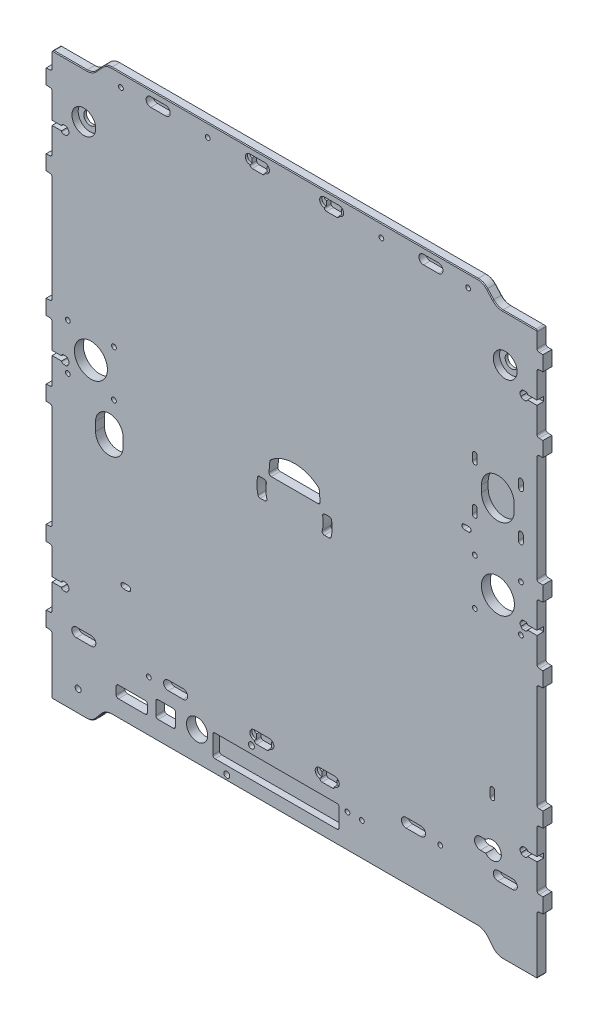
SolidWorks part; units mm, degrees
ref_plane "Alzado" through (0, 0, 0) normal (0, 0, 1) x (1, 0, 0)
ref_plane "Planta" through (0, 0, 0) normal (0, 1, 0) x (1, 0, 0)
ref_plane "Vista lateral" through (0, 0, 0) normal (1, 0, 0) x (0, 0, -1)
ref_plane "Plano1" through (0, 0, 3) normal (0, 0, 1) x (1, 0, 0)
sketch "Croquis1" plane through (0, 0, 3) normal (0, 0, 1) x (1, 0, 0)
  line L0 (-167.1, 194) -> (-167.1, -194)
  line L1 (-167.1, -194) -> (167.1, -194)
  line L2 (167.1, -194) -> (167.1, 194)
  line L3 (167.1, 194) -> (-167.1, 194)
  dimension "D1" = 334.2
  dimension "D2" = 388
extrude "Saliente-Extruir1" add sketch "Croquis1" against normal blind 6
sketch "Croquis2" plane through (0, 0, 3) normal (0, 0, 1) x (1, 0, 0)
  line L0 (-17, -151.6) -> (-17, -150.1)
  line L1 (-17, -143.9) -> (-27, -143.9)
  line L2 (-27, -150.1) -> (-27, -151.6)
  line L3 (-27, -151.6) -> (-17, -151.6)
  line L5 (167.1, 194) -> (-167.1, 194) construction
  arc A0 (-17, -150.1) -> (-17, -143.9) centre (-17, -147) ccw
  arc A1 (-27, -143.9) -> (-27, -150.1) centre (-27, -147) ccw
  dimension "D1" = 3.1
  dimension "D3" = 345.6
extrude "Cortar-Extruir1" cut sketch "Croquis2" against normal blind 1.5
sketch "Croquis3" plane through (0, 0, 1.5) normal (0, 0, 1) x (1, 0, 0)
  line L0 (-17, -143.9) -> (-27, -143.9)
  line L1 (-27, -146.9) -> (-27, -151.6)
  line L2 (-27, -151.6) -> (-17, -151.6)
  line L3 (-17, -151.6) -> (-17, -146.9)
  arc A0 (-17, -146.9) -> (-17, -143.9) centre (-17, -145.4) ccw
  arc A1 (-27, -143.9) -> (-27, -146.9) centre (-27, -145.4) ccw
  dimension "D1" = 1.5
  dimension "D2" = 1.5
extrude "Cortar-Extruir2" cut sketch "Croquis3" against normal blind 3
sketch "Croquis4" plane through (0, 0, 3) normal (0, 0, 1) x (1, 0, 0)
  line L0 (-20, 182.4) -> (-20, 183.9)
  line L1 (-20, 190.1) -> (-30, 190.1)
  line L2 (-30, 183.9) -> (-30, 182.4)
  line L3 (-30, 182.4) -> (-20, 182.4)
  line L4 (-27, -150.1) -> (-27, -151.6) construction
  line L5 (-27, -151.6) -> (-17, -151.6) construction
  arc A0 (-20, 183.9) -> (-20, 190.1) centre (-20, 187) ccw
  arc A1 (-30, 190.1) -> (-30, 183.9) centre (-30, 187) ccw
  dimension "D1" = 3.1
  dimension "D2" = 7
  dimension "D3" = 3
  dimension "D4" = 334
  dimension "D5" = 338.6
extrude "Cortar-Extruir3" cut sketch "Croquis4" against normal blind 1.5
sketch "Croquis5" plane through (0, 0, 1.5) normal (0, 0, 1) x (1, 0, 0)
  line L0 (-30, 187.1) -> (-30, 182.4)
  line L1 (-30, 182.4) -> (-20, 182.4)
  line L2 (-20, 182.4) -> (-20, 187.1)
  line L3 (-20, 190.1) -> (-30, 190.1)
  line L4 (-20, 182.4) -> (-20, 183.9) construction
  arc A0 (-30, 190.1) -> (-30, 187.1) centre (-30, 188.6) ccw
  arc A1 (-20, 187.1) -> (-20, 190.1) centre (-20, 188.6) ccw
  dimension "D1" = 1.5
  dimension "D2" = 10
extrude "Cortar-Extruir4" cut sketch "Croquis5" against normal blind 3
sketch "Croquis6" plane through (0, 0, -3) normal (0, 0, -1) x (-1, 0, 0)
  line L0 (167.1, 121.8397) -> (167.1, 161.5603)
  line L1 (167.1, 161.5603) -> (163.1, 161.5603)
  line L2 (163.1, 161.5603) -> (163.1, 121.8397)
  line L3 (163.1, 121.8397) -> (167.1, 121.8397)
  line L4 (-167.1, -194) -> (-167.1, 194) construction
  line L5 (-167.1, 194) -> (167.1, 194) construction
  dimension "D1" = 330.2
  dimension "D2" = 334.2
  dimension "D3" = 32.4397
  dimension "D4" = 72.1603
extrude "Cortar-Extruir5" cut sketch "Croquis6" against normal through all
sketch "Croquis7" plane through (0, 0, -3) normal (0, 0, -1) x (-1, 0, 0)
  line L0 (167.1, -12.3603) -> (167.1, 27.3603)
  line L1 (167.1, 27.3603) -> (163.1, 27.3603)
  line L2 (163.1, 27.3603) -> (163.1, -12.3603)
  line L3 (163.1, -12.3603) -> (167.1, -12.3603)
  line L4 (163.1, 161.5603) -> (163.1, 121.8397) construction
  line L5 (167.1, 161.5603) -> (163.1, 161.5603) construction
  dimension "D1" = 4
  dimension "D2" = 134.2
  dimension "D3" = 173.9206
extrude "Cortar-Extruir6" cut sketch "Croquis7" against normal through all
sketch "Croquis8" plane through (0, 0, -3) normal (0, 0, -1) x (-1, 0, 0)
  line L0 (167.1, -144.0603) -> (167.1, -104.3397)
  line L1 (167.1, -104.3397) -> (163.1, -104.3397)
  line L2 (163.1, -104.3397) -> (163.1, -144.0603)
  line L3 (163.1, -144.0603) -> (167.1, -144.0603)
  line L4 (167.1, 121.8397) -> (167.1, 27.3603) construction
  line L5 (163.1, 121.8397) -> (167.1, 121.8397) construction
  dimension "D1" = 4
  dimension "D2" = 226.1794
  dimension "D3" = 265.9
extrude "Cortar-Extruir7" cut sketch "Croquis8" against normal through all
sketch "Croquis9" plane through (0, 0, 3) normal (0, 0, 1) x (1, 0, 0)
  line L0 (-163.1, -125.8) -> (-156.779, -125.8)
  line L1 (-155.3, -127.05) -> (-153.9, -127.05)
  line L2 (-152.421, -125.8) -> (-152.421, -125.6375)
  line L3 (-152.421, -122.9625) -> (-152.421, -122.8)
  line L4 (-153.9, -121.55) -> (-155.3, -121.55)
  line L5 (-156.779, -122.8) -> (-163.1, -122.8)
  line L6 (-163.1, -122.8) -> (-163.1, -125.8)
  line L7 (-167.1, -144.0603) -> (-167.1, -194) construction
  line L8 (-167.1, -194) -> (167.1, -194) construction
  arc A0 (-156.779, -125.8) -> (-155.3, -127.05) centre (-155.3, -125.55) ccw
  arc A1 (-153.9, -127.05) -> (-152.421, -125.8) centre (-153.9, -125.55) ccw
  arc A2 (-152.421, -125.6375) -> (-152.421, -122.9625) centre (-153.1, -124.3) ccw
  arc A3 (-152.421, -122.8) -> (-153.9, -121.55) centre (-153.9, -123.05) ccw
  arc A4 (-155.3, -121.55) -> (-156.779, -122.8) centre (-155.3, -123.05) ccw
  dimension "D1" = 1.5
  dimension "D2" = 1.5
  dimension "D3" = 1.5
  dimension "D4" = 4
  dimension "D5" = 10.321
  dimension "D6" = 11.8
  dimension "D7" = 13.2
  dimension "D8" = 14
  dimension "D9" = 68.3625
extrude "Cortar-Extruir8" cut sketch "Croquis9" against normal blind 4.5
sketch "Croquis10" plane through (0, 0, 3) normal (0, 0, 1) x (1, 0, 0)
  line L0 (-163.1, 6.1) -> (-156.7795, 6.1)
  line L1 (-155.3004, 4.85) -> (-153.9004, 4.85)
  line L2 (-152.4214, 6.1) -> (-152.4214, 6.2625)
  line L3 (-152.4214, 8.9375) -> (-152.4214, 9.1)
  line L4 (-153.9004, 10.35) -> (-155.3004, 10.35)
  line L5 (-156.7795, 9.1) -> (-163.1, 9.1)
  line L6 (-163.1, 9.1) -> (-163.1, 6.1)
  line L7 (-167.1, -144.0603) -> (-167.1, -194) construction
  line L8 (-167.1, -194) -> (167.1, -194) construction
  arc A0 (-156.7795, 6.1) -> (-155.3004, 4.85) centre (-155.3004, 6.35) ccw
  arc A1 (-153.9004, 4.85) -> (-152.4214, 6.1) centre (-153.9004, 6.35) ccw
  arc A2 (-152.4214, 6.2625) -> (-152.4214, 8.9375) centre (-153.1004, 7.6) ccw
  arc A3 (-152.4214, 9.1) -> (-153.9004, 10.35) centre (-153.9004, 8.85) ccw
  arc A4 (-155.3004, 10.35) -> (-156.7795, 9.1) centre (-155.3004, 8.85) ccw
  dimension "D1" = 1.5
  dimension "D2" = 1.5
  dimension "D3" = 1.5
  dimension "D4" = 4
  dimension "D5" = 200.2625
  dimension "D6" = 201.6
  dimension "D8" = 13.9996
extrude "Cortar-Extruir9" cut sketch "Croquis10" against normal blind 4.5
sketch "Croquis11" plane through (0, 0, 3) normal (0, 0, 1) x (1, 0, 0)
  line L0 (-163.1, 140.2) -> (-156.779, 140.2)
  line L1 (-155.3, 138.95) -> (-153.9, 138.95)
  line L2 (-152.421, 140.2) -> (-152.421, 140.3625)
  line L3 (-152.421, 143.0375) -> (-152.421, 143.2)
  line L4 (-153.9, 144.45) -> (-155.3, 144.45)
  line L5 (-156.779, 143.2) -> (-163.1, 143.2)
  line L6 (-163.1, 143.2) -> (-163.1, 140.2)
  line L7 (-167.1, -12.3603) -> (-167.1, -104.3397) construction
  line L8 (-155.3, -127.05) -> (-153.9, -127.05) construction
  arc A0 (-156.779, 140.2) -> (-155.3, 138.95) centre (-155.3, 140.45) ccw
  arc A1 (-153.9, 138.95) -> (-152.421, 140.2) centre (-153.9, 140.45) ccw
  arc A2 (-152.421, 140.3625) -> (-152.421, 143.0375) centre (-153.1, 141.7) ccw
  arc A3 (-152.421, 143.2) -> (-153.9, 144.45) centre (-153.9, 142.95) ccw
  arc A4 (-155.3, 144.45) -> (-156.779, 143.2) centre (-155.3, 142.95) ccw
  dimension "D1" = 1.5
  dimension "D2" = 1.5
  dimension "D3" = 1.5
  dimension "D4" = 4
  dimension "D5" = 266
  dimension "D6" = 267.25
  dimension "D7" = 267.4125
  dimension "D8" = 14
  dimension "D9" = 268.75
  dimension "D10" = 270
extrude "Cortar-Extruir10" cut sketch "Croquis11" against normal blind 4.5
sketch "Croquis12" plane through (0, 0, -3) normal (0, 0, -1) x (-1, 0, 0)
  line L0 (126.9478, 194) -> (126.9478, 184)
  line L1 (126.9478, 184) -> (167.1, 184)
  line L2 (167.1, 184) -> (167.1, 194)
  line L3 (167.1, 194) -> (126.9478, 194)
  line L4 (163.1, 27.3603) -> (163.1, -12.3603) construction
  line L5 (167.1, 27.3603) -> (163.1, 27.3603) construction
  dimension "D1" = 4
  dimension "D2" = 36.1522
  dimension "D3" = 156.6397
  dimension "D4" = 166.6397
extrude "Cortar-Extruir11" cut sketch "Croquis12" against normal through all
sketch "Croquis13" plane through (0, 0, -3) normal (0, 0, -1) x (-1, 0, 0)
  line L0 (163.1, 171.8397) -> (167.1, 171.8397)
  line L1 (167.1, 171.8397) -> (167.1, 184)
  line L2 (167.1, 184) -> (163.1, 184)
  line L3 (163.1, 184) -> (163.1, 171.8397)
  line L4 (167.1, -144.0603) -> (167.1, -194) construction
  line L5 (167.1, -194) -> (-167.1, -194) construction
  dimension "D1" = 4
  dimension "D2" = 365.8397
  dimension "D3" = 378
extrude "Cortar-Extruir12" cut sketch "Croquis13" against normal through all
sketch "Croquis14" plane through (0, 0, -3) normal (0, 0, -1) x (-1, 0, 0)
  line L0 (167.1, 37.6397) -> (167.1, 111.5603)
  line L1 (167.1, 111.5603) -> (163.1, 111.5603)
  line L2 (163.1, 111.5603) -> (163.1, 37.6397)
  line L3 (163.1, 37.6397) -> (167.1, 37.6397)
  line L4 (167.1, -144.0603) -> (167.1, -194) construction
  line L5 (167.1, -194) -> (-167.1, -194) construction
  dimension "D1" = 4
  dimension "D2" = 231.6397
  dimension "D3" = 305.5603
extrude "Cortar-Extruir13" cut sketch "Croquis14" against normal through all
sketch "Croquis15" plane through (0, 0, -3) normal (0, 0, -1) x (-1, 0, 0)
  line L0 (167.1, -94.0603) -> (167.1, -22.6397)
  line L1 (167.1, -22.6397) -> (163.1, -22.6397)
  line L2 (163.1, -22.6397) -> (163.1, -94.0603)
  line L3 (163.1, -94.0603) -> (167.1, -94.0603)
  line L4 (167.1, 171.8397) -> (167.1, 161.5603) construction
  line L5 (126.9478, 184) -> (163.1, 184) construction
  dimension "D1" = 4
  dimension "D2" = 206.6397
  dimension "D3" = 278.0603
extrude "Cortar-Extruir14" cut sketch "Croquis15" against normal through all
sketch "Croquis16" plane through (0, 0, -3) normal (0, 0, -1) x (-1, 0, 0)
  line L0 (167.1, -154.3397) -> (163.1, -154.3397)
  line L1 (163.1, -154.3397) -> (163.1, -194)
  line L2 (163.1, -194) -> (167.1, -194)
  line L3 (167.1, -194) -> (167.1, -154.3397)
  line L4 (167.1, 121.8397) -> (167.1, 111.5603) construction
  line L5 (163.1, 121.8397) -> (167.1, 121.8397) construction
  dimension "D1" = 4
  dimension "D2" = 276.1794
  dimension "D3" = 315.8397
extrude "Cortar-Extruir15" cut sketch "Croquis16" against normal through all
sketch "Croquis17" plane through (0, 0, -3) normal (0, 0, -1) x (-1, 0, 0)
  line L0 (126.9478, -194) -> (126.9478, -183.0928)
  line L1 (126.9478, -183.0928) -> (-126.9478, -183.0928)
  line L2 (-126.9478, -183.0928) -> (-126.9478, -194)
  line L3 (-126.9478, -194) -> (126.9478, -194)
  line L4 (167.1, -144.0603) -> (167.1, -154.3397) construction
  line L5 (163.1, -194) -> (-167.1, -194) construction
  dimension "D1" = 40.1522
  dimension "D2" = 294.0478
  dimension "D3" = 10.9072
extrude "Cortar-Extruir16" cut sketch "Croquis17" against normal through all
sketch "Croquis18" plane through (0, 0, 3) normal (0, 0, 1) x (1, 0, 0)
  line L0 (-99.03, -171.55) -> (-99.03, -163.55)
  line L1 (-99.03, -163.55) -> (-120.03, -163.55)
  line L2 (-120.03, -163.55) -> (-120.03, -171.55)
  line L3 (-120.03, -171.55) -> (-99.03, -171.55)
  line L4 (167.1, -194) -> (167.1, 194) construction
  line L5 (126.9478, -194) -> (167.1, -194) construction
  dimension "D1" = 266.13
  dimension "D2" = 287.13
  dimension "D3" = 22.45
  dimension "D4" = 30.45
extrude "Cortar-Extruir17" cut sketch "Croquis18" against normal through all
sketch "Croquis19" plane through (0, 0, 3) normal (0, 0, 1) x (1, 0, 0)
  line L0 (-80.15, -170.25) -> (-80.15, -158.75)
  line L1 (-80.15, -158.75) -> (-93.35, -158.75)
  line L2 (-93.35, -158.75) -> (-93.35, -170.25)
  line L3 (-93.35, -170.25) -> (-80.15, -170.25)
  line L4 (167.1, -194) -> (167.1, 194) construction
  line L5 (126.9478, -194) -> (167.1, -194) construction
  dimension "D1" = 247.25
  dimension "D2" = 260.45
  dimension "D3" = 23.75
  dimension "D4" = 35.25
extrude "Cortar-Extruir18" cut sketch "Croquis19" against normal through all
sketch "Croquis20" plane through (0, 0, 3) normal (0, 0, 1) x (1, 0, 0)
  line L0 (153.8846, 55.25) -> (153.8846, 59.75)
  line L1 (150.6846, 59.75) -> (150.6846, 55.25)
  line L2 (167.1, -194) -> (167.1, 194) construction
  line L3 (126.9478, -194) -> (167.1, -194) construction
  arc A0 (153.8846, 59.75) -> (150.6846, 59.75) centre (152.2846, 59.75) ccw
  arc A1 (150.6846, 55.25) -> (153.8846, 55.25) centre (152.2846, 55.25) ccw
  dimension "D1" = 1.6
  dimension "D2" = 14.8154
  dimension "D3" = 249.25
  dimension "D4" = 253.75
extrude "Cortar-Extruir19" cut sketch "Croquis20" against normal through all
sketch "Croquis21" plane through (0, 0, 3) normal (0, 0, 1) x (1, 0, 0)
  line L0 (150.6846, 90.75) -> (150.6846, 86.25)
  line L1 (153.8846, 86.25) -> (153.8846, 90.75)
  line L2 (167.1, -194) -> (167.1, 194) construction
  line L3 (126.9478, -194) -> (167.1, -194) construction
  arc A0 (150.6846, 86.25) -> (153.8846, 86.25) centre (152.2846, 86.25) ccw
  arc A1 (153.8846, 90.75) -> (150.6846, 90.75) centre (152.2846, 90.75) ccw
  dimension "D1" = 1.6
  dimension "D2" = 14.8154
  dimension "D3" = 280.25
  dimension "D4" = 284.75
extrude "Cortar-Extruir20" cut sketch "Croquis21" against normal through all
sketch "Croquis22" plane through (0, 0, 3) normal (0, 0, 1) x (1, 0, 0)
  line L0 (122.8846, 55.25) -> (122.8846, 59.75)
  line L1 (119.6846, 59.75) -> (119.6846, 55.25)
  line L2 (167.1, -194) -> (167.1, 194) construction
  line L3 (126.9478, -194) -> (167.1, -194) construction
  arc A0 (122.8846, 59.75) -> (119.6846, 59.75) centre (121.2846, 59.75) ccw
  arc A1 (119.6846, 55.25) -> (122.8846, 55.25) centre (121.2846, 55.25) ccw
  dimension "D1" = 1.6
  dimension "D2" = 45.8154
  dimension "D3" = 249.25
  dimension "D4" = 253.75
extrude "Cortar-Extruir21" cut sketch "Croquis22" against normal through all
sketch "Croquis23" plane through (0, 0, 3) normal (0, 0, 1) x (1, 0, 0)
  line L0 (119.6846, 90.75) -> (119.6846, 86.25)
  line L1 (122.8846, 86.25) -> (122.8846, 90.75)
  line L2 (167.1, -194) -> (167.1, 194) construction
  line L3 (126.9478, -194) -> (167.1, -194) construction
  arc A0 (119.6846, 86.25) -> (122.8846, 86.25) centre (121.2846, 86.25) ccw
  arc A1 (122.8846, 90.75) -> (119.6846, 90.75) centre (121.2846, 90.75) ccw
  dimension "D1" = 1.6
  dimension "D2" = 45.8154
  dimension "D3" = 280.25
  dimension "D4" = 284.75
extrude "Cortar-Extruir22" cut sketch "Croquis23" against normal through all
sketch "Croquis24" plane through (0, 0, 3) normal (0, 0, 1) x (1, 0, 0)
  line L0 (-133.85, -17.6) -> (-133.85, -23.6)
  line L1 (-115.35, -23.6) -> (-115.35, -17.6)
  line L2 (167.1, -194) -> (167.1, 194) construction
  line L3 (126.9478, -194) -> (167.1, -194) construction
  arc A0 (-133.85, -23.6) -> (-115.35, -23.6) centre (-124.6, -23.6) ccw
  arc A1 (-115.35, -17.6) -> (-133.85, -17.6) centre (-124.6, -17.6) ccw
  dimension "D1" = 9.25
  dimension "D2" = 291.7
  dimension "D3" = 170.4
  dimension "D4" = 176.4
extrude "Cortar-Extruir23" cut sketch "Croquis24" against normal through all
sketch "Croquis25" plane through (0, 0, 3) normal (0, 0, 1) x (1, 0, 0)
  line L0 (-17.3459, 9.2964) -> (17.3459, 9.2964)
  line L1 (17.3459, 9.2964) -> (16.5432, 18.4711)
  line L2 (-16.5432, 18.4711) -> (-17.3459, 9.2964)
  line L3 (167.1, -194) -> (167.1, 194) construction
  line L4 (126.9478, -194) -> (167.1, -194) construction
  arc A0 (16.5432, 18.4711) -> (-16.5432, 18.4711) centre (0, 0) ccw
  dimension "D1" = 24.7964
  dimension "D2" = 149.7541
  dimension "D3" = 150.5568
  dimension "D4" = 167.1
  dimension "D5" = 194
  dimension "D6" = 184.4459
  dimension "D7" = 203.2964
extrude "Cortar-Extruir24" cut sketch "Croquis25" against normal through all
sketch "Croquis26" plane through (0, 0, 3) normal (0, 0, 1) x (1, 0, 0)
  line L0 (-24.3086, -7) -> (-20.0559, -7)
  line L1 (-18.496, 5.5) -> (-24.6913, 5.5)
  line L2 (167.1, -194) -> (167.1, 194) construction
  line L3 (126.9478, -194) -> (167.1, -194) construction
  arc A0 (-24.6913, 5.5) -> (-24.3086, -7) centre (0, 0) ccw
  arc A1 (-20.0559, -7) -> (-18.6094, -5.1033) centre (-20.0559, -5.5) ccw
  arc A2 (-18.6094, -5.1033) -> (-18.496, 5.5) centre (0, 0) cw
  dimension "D1" = 25.2964
  dimension "D2" = 1.5
  dimension "D3" = 19.2964
  dimension "D4" = 167.1
  dimension "D5" = 185.596
  dimension "D6" = 185.7094
  dimension "D7" = 187
extrude "Cortar-Extruir25" cut sketch "Croquis26" against normal through all
sketch "Croquis27" plane through (0, 0, 3) normal (0, 0, 1) x (1, 0, 0)
  line L0 (125.1, -138) -> (128.6279, -138)
  line L1 (128.6279, -130) -> (125.1, -130)
  line L2 (167.1, -194) -> (167.1, 194) construction
  arc A0 (128.6279, -138) -> (128.6279, -130) centre (133.1, -134) cw
  arc A1 (125.1, -130) -> (125.1, -138) centre (125.1, -134) ccw
  dimension "D1" = 6
  dimension "D2" = 4
  dimension "D3" = 34
  dimension "D5" = 42
extrude "Cortar-Extruir26" cut sketch "Croquis27" against normal through all
sketch "Croquis28" plane through (0, 0, 3) normal (0, 0, 1) x (1, 0, 0)
  line L0 (131.6, -98.5) -> (131.6, -103.5)
  line L1 (134.6, -103.5) -> (134.6, -98.5)
  line L2 (167.1, -194) -> (167.1, 194) construction
  line L3 (126.9478, -194) -> (167.1, -194) construction
  arc A0 (131.6, -103.5) -> (134.6, -103.5) centre (133.1, -103.5) ccw
  arc A1 (134.6, -98.5) -> (131.6, -98.5) centre (133.1, -98.5) ccw
  dimension "D1" = 1.5
  dimension "D2" = 34
  dimension "D3" = 90.5
  dimension "D4" = 95.5
extrude "Cortar-Extruir27" cut sketch "Croquis28" against normal through all
sketch "Croquis29" plane through (0, 0, 3) normal (0, 0, 1) x (1, 0, 0)
  line L0 (114.1289, 43.4) -> (117.1289, 43.4)
  line L1 (117.1289, 46.6) -> (114.1289, 46.6)
  line L2 (167.1, -194) -> (167.1, 194) construction
  line L3 (126.9478, -194) -> (167.1, -194) construction
  arc A0 (117.1289, 43.4) -> (117.1289, 46.6) centre (117.1289, 45) ccw
  arc A1 (114.1289, 46.6) -> (114.1289, 43.4) centre (114.1289, 45) ccw
  dimension "D1" = 1.6
  dimension "D2" = 49.9711
  dimension "D3" = 52.9711
  dimension "D4" = 239
extrude "Cortar-Extruir28" cut sketch "Croquis29" against normal through all
sketch "Croquis30" plane through (0, 0, -3) normal (0, 0, -1) x (-1, 0, 0)
  line L0 (115, -102.25) -> (112, -102.25)
  line L1 (112, -105.75) -> (115, -105.75)
  line L2 (133.85, -17.6) -> (133.85, -23.6) construction
  line L3 (-125.1, -138) -> (-128.6279, -138) construction
  arc A0 (112, -102.25) -> (112, -105.75) centre (112, -104) ccw
  arc A1 (115, -105.75) -> (115, -102.25) centre (115, -104) ccw
  dimension "D1" = 1.75
  dimension "D2" = 18.85
  dimension "D3" = 21.85
  dimension "D4" = 34
extrude "Cortar-Extruir29" cut sketch "Croquis30" against normal through all
sketch "Croquis31" plane through (0, 0, 3) normal (0, 0, 1) x (1, 0, 0)
  line L0 (147.7846, 70.75) -> (147.7846, 75.25)
  line L1 (125.7846, 75.25) -> (125.7846, 70.75)
  line L2 (167.1, -194) -> (167.1, 194) construction
  line L3 (126.9478, -194) -> (167.1, -194) construction
  arc A0 (125.7846, 70.75) -> (147.7846, 70.75) centre (136.7846, 70.75) ccw
  arc A1 (147.7846, 75.25) -> (125.7846, 75.25) centre (136.7846, 75.25) ccw
  dimension "D1" = 11
  dimension "D2" = 30.3154
  dimension "D3" = 264.75
  dimension "D4" = 269.25
extrude "Cortar-Extruir30" cut sketch "Croquis31" against normal blind 4.5
sketch "Croquis32" plane through (0, 0, 3) normal (0, 0, 1) x (1, 0, 0)
  line L0 (-75, -143.9) -> (-85, -143.9)
  line L1 (-85, -150.1) -> (-75, -150.1)
  line L2 (167.1, -194) -> (167.1, 194) construction
  line L3 (126.9478, -194) -> (167.1, -194) construction
  arc A0 (-85, -143.9) -> (-85, -150.1) centre (-85, -147) ccw
  arc A1 (-75, -150.1) -> (-75, -143.9) centre (-75, -147) ccw
  dimension "D1" = 3.1
  dimension "D2" = 242.1
  dimension "D3" = 252.1
  dimension "D4" = 47
extrude "Cortar-Extruir31" cut sketch "Croquis32" against normal blind 4.5
sketch "Croquis33" plane through (0, 0, 3) normal (0, 0, 1) x (1, 0, 0)
  line L0 (-146.8, -150.1) -> (-136.8, -150.1)
  line L1 (-136.8, -143.9) -> (-146.8, -143.9)
  line L2 (167.1, -194) -> (167.1, 194) construction
  line L3 (126.9478, -194) -> (167.1, -194) construction
  arc A0 (-136.8, -150.1) -> (-136.8, -143.9) centre (-136.8, -147) ccw
  arc A1 (-146.8, -143.9) -> (-146.8, -150.1) centre (-146.8, -147) ccw
  dimension "D1" = 3.1
  dimension "D2" = 303.9
  dimension "D3" = 313.9
  dimension "D4" = 47
extrude "Cortar-Extruir32" cut sketch "Croquis33" against normal blind 4.5
sketch "Croquis34" plane through (0, 0, 3) normal (0, 0, 1) x (1, 0, 0)
  line L0 (-86.75, 190.1) -> (-96.75, 190.1)
  line L1 (-96.75, 183.9) -> (-86.75, 183.9)
  line L2 (167.1, -194) -> (167.1, 194) construction
  line L3 (126.9478, -194) -> (167.1, -194) construction
  arc A0 (-96.75, 190.1) -> (-96.75, 183.9) centre (-96.75, 187) ccw
  arc A1 (-86.75, 183.9) -> (-86.75, 190.1) centre (-86.75, 187) ccw
  dimension "D1" = 3.1
  dimension "D2" = 253.85
  dimension "D3" = 263.85
  dimension "D4" = 381
extrude "Cortar-Extruir33" cut sketch "Croquis34" against normal blind 4.5
mirror "Simetría1" about plane through (0, 0, 0) normal (1, 0, 0) of "Cortar-Extruir9", "Cortar-Extruir1", "Cortar-Extruir2", "Cortar-Extruir3", "Cortar-Extruir4", "Cortar-Extruir5", "Cortar-Extruir6", "Cortar-Extruir7", "Cortar-Extruir8", "Cortar-Extruir10", "Cortar-Extruir11", "Cortar-Extruir12", "Cortar-Extruir13", "Cortar-Extruir14", "Cortar-Extruir15", "Cortar-Extruir25", "Cortar-Extruir31", "Cortar-Extruir32", "Cortar-Extruir33"
sketch "Croquis36" plane through (0, 0, 3) normal (0, 0, 1) x (1, 0, 0)
  line L0 (-55, -159) -> (-55, -174)
  line L1 (-55, -174) -> (30, -174)
  line L2 (30, -174) -> (30, -159)
  line L3 (30, -159) -> (-55, -159)
  line L4 (167.1, -22.6397) -> (167.1, -12.3603) construction
  line L5 (20, 190.1) -> (30, 190.1) construction
  dimension "D1" = 137.1
  dimension "D2" = 222.1
  dimension "D3" = 349.1
  dimension "D4" = 364.1
extrude "Cortar-Extruir34" cut sketch "Croquis36" against normal blind 4.5
draft "Ángulo de salida1" type of draft neutral plane draft angle 2 faces to draft 1 face at (165.1, -154.3397, 0) neutral plane through (163.1, -154.3397, 3) neutral plane normal (1, 0, 0) parameters "D1"=2
draft "Ángulo de salida2" type of draft neutral plane draft angle 2 faces to draft 1 face at (165.1, 171.8397, 0) neutral plane through (163.1, 184, 3) neutral plane normal (1, 0, 0) parameters "D1"=2
draft "Ángulo de salida3" type of draft neutral plane draft angle 2 faces to draft 1 face at (-165.1, 171.8397, 0) neutral plane through (-163.1, 184, 3) neutral plane normal (-1, 0, 0) parameters "D1"=2
draft "Ángulo de salida4" type of draft neutral plane draft angle 2 faces to draft 1 face at (-165.1, -154.3397, 0) neutral plane through (-163.1, -154.3397, 3) neutral plane normal (-1, 0, 0) parameters "D1"=2
draft "Ángulo de salida5" type of draft neutral plane draft angle 2 faces to draft 2 face at (165.1, -94.0603, 0) face at (165.1, -22.6397, 0) neutral plane through (163.1, -22.6397, 3) neutral plane normal (1, 0, 0) parameters "D1"=2
draft "Ángulo de salida6" type of draft neutral plane draft angle 2 faces to draft 2 face at (165.1, 37.6397, 0) face at (165.1, 111.5603, 0) neutral plane through (163.1, 111.5603, 3) neutral plane normal (1, 0, 0) parameters "D1"=2
draft "Ángulo de salida7" type of draft neutral plane draft angle 2 faces to draft 2 face at (-165.1, 111.5603, 0) face at (-165.1, 37.6397, 0) neutral plane through (-163.1, 111.5603, 3) neutral plane normal (-1, 0, 0) parameters "D1"=2
draft "Ángulo de salida8" type of draft neutral plane draft angle 2 faces to draft 2 face at (-165.1, -22.6397, 0) face at (-165.1, -94.0603, 0) neutral plane through (-163.1, -22.6397, 3) neutral plane normal (-1, 0, 0) parameters "D1"=2
draft "Ángulo de salida9" type of draft neutral plane draft angle 2 faces to draft 2 face at (165.1, -144.0603, 0) face at (165.1, -104.3397, 0) neutral plane through (163.1, -104.3397, 3) neutral plane normal (1, 0, 0) parameters "D1"=2
draft "Ángulo de salida10" type of draft neutral plane draft angle 2 faces to draft 2 face at (165.1, -12.3603, 0) face at (165.1, 27.3603, 0) neutral plane through (163.1, 27.3603, 3) neutral plane normal (1, 0, 0) parameters "D1"=2
draft "Ángulo de salida11" type of draft neutral plane draft angle 2 faces to draft 2 face at (165.1, 121.8397, 0) face at (165.1, 161.5603, 0) neutral plane through (163.1, 161.5603, 3) neutral plane normal (1, 0, 0) parameters "D1"=2
draft "Ángulo de salida12" type of draft neutral plane draft angle 42.465 faces to draft 2 face at (126.9478, 189, 0) face at (-126.9478, 189, 0) neutral plane through (167.1, 194, -3) neutral plane normal (0, 1, 0) parameters "D1"=42.465
draft "Ángulo de salida13" type of draft neutral plane draft angle 2 faces to draft 2 face at (-165.1, 161.5603, 0) face at (-165.1, 121.8397, 0) neutral plane through (-163.1, 161.5603, 3) neutral plane normal (-1, 0, 0) parameters "D1"=2
draft "Ángulo de salida14" type of draft neutral plane draft angle 2 faces to draft 2 face at (-165.1, 27.3603, 0) face at (-165.1, -12.3603, 0) neutral plane through (-163.1, 27.3603, 3) neutral plane normal (-1, 0, 0) parameters "D1"=2
draft "Ángulo de salida15" type of draft neutral plane draft angle 2 faces to draft 2 face at (-165.1, -104.3397, 0) face at (-165.1, -144.0603, 0) neutral plane through (-163.1, -104.3397, 3) neutral plane normal (-1, 0, 0) parameters "D1"=2
draft "Ángulo de salida16" type of draft neutral plane draft angle 40 faces to draft 2 face at (126.9478, -188.5464, 0) face at (-126.9478, -188.5464, 0) neutral plane through (-126.9478, -183.0928, 3) neutral plane normal (0, -1, 0) parameters "D1"=40
ref_plane "Plano2" through (0, -134, 0) normal (0, 1, 0) x (1, 0, 0)
sketch "Croquis37" plane through (0, -134, 0) normal (0, 1, 0) x (1, 0, 0)
  line L0 (139.1, 3) -> (133.1, 3)
  line L1 (133.1, 3) -> (133.1, -3)
  line L2 (133.1, -3) -> (139.1, -3)
  line L3 (139.1, -3) -> (139.1, 3)
  line L4 (133.1, 3) -> (133.1, -3) construction
  dimension "D1" = 6
  dimension "D2" = 6
revolve "Cortar-Revolución1" cut sketch "Croquis37" angle 360 about L4
hole_wizard "Taladro de margen para M121" positions "Croquis39" profile "Croquis38" hole size "M12" standard "Ansi Metric"
sketch "Croquis39" plane through (0, 0, -3) normal (0, 0, -1) x (-1, 0, 0)
  point P0 (65.55, -163)
sketch "Croquis38" plane through (-65.55, -163, -3) normal (1, 0, 0) x (0, 1, 0)
  line L0 (0, 0) -> (0, 6)
  line L1 (0, 6) -> (7.15, 6)
  line L2 (7.15, 6) -> (7.15, 0)
  line L5 (7.15, 0) -> (0, 0)
  line L11 (0, -6.35) -> (0, 107.95) construction
  dimension "Diámetro de taladro hasta el siguiente" = 14.3
  dimension "Profundidad de taladro hasta el siguiente" = 6
hole_wizard "Taladro de margen para M201" positions "Croquis41" profile "Croquis40" hole size "M20" standard "Ansi Metric"
sketch "Croquis41" plane through (0, 0, -3) normal (0, 0, -1) x (-1, 0, 0)
  point P0 (137, 16.5)
  point P1 (-136.7965, 16.5)
sketch "Croquis40" plane through (-137, 16.5, -3) normal (1, 0, 0) x (0, 1, 0)
  line L0 (0, 0) -> (0, 6)
  line L1 (0, 6) -> (11.1, 6)
  line L2 (11.1, 6) -> (11.1, 0)
  line L5 (11.1, 0) -> (0, 0)
  line L11 (0, -6.35) -> (0, 107.95) construction
  dimension "Diámetro de taladro hasta el siguiente" = 22.2
  dimension "Profundidad de taladro hasta el siguiente" = 6
hole_wizard "Diámetro de taladro Ø3.2 (3.2)1" positions "Croquis43" profile "Croquis42" hole size "Ø3.2" standard "Ansi Metric"
sketch "Croquis43" plane through (0, 0, 3) normal (0, 0, 1) x (1, 0, 0)
  point P0 (98, -148.55)
  point P1 (116.8, 185.45)
  point P2 (58.439, 185.45)
sketch "Croquis42" plane through (98, -148.55, 3) normal (1, 0, 0) x (0, -1, 0)
  line L0 (0, 0) -> (0, 6)
  line L1 (0, 6) -> (1.6, 6)
  line L2 (1.6, 6) -> (1.6, 0)
  line L5 (1.6, 0) -> (0, 0)
  line L11 (0, -6.35) -> (0, 107.95) construction
  dimension "Diámetro de taladro hasta el siguiente" = 3.2
  dimension "Profundidad de taladro hasta el siguiente" = 6
hole_wizard "Diámetro de taladro Ø3.2 (3.2)2" positions "Croquis45" profile "Croquis44" hole size "Ø3.2" standard "Ansi Metric"
sketch "Croquis45" plane through (0, 0, -3) normal (0, 0, -1) x (-1, 0, 0)
  point P0 (-121.2965, 1)
  point P1 (-152.2965, 32)
  point P2 (98, -148.55)
  point P3 (116.8, 185.45)
  point P4 (58.439, 185.45)
  point P5 (121.5, 32)
  point P6 (152.5, 32)
  point P7 (152.5, 1)
  point P8 (121.5, 1)
  point P9 (-35.6, -160.5)
  point P10 (-45.3, -160.5)
  point P11 (-121.2965, 32)
  point P12 (-152.2965, 1)
sketch "Croquis44" plane through (121.2965, 1, -3) normal (1, 0, 0) x (0, 1, 0)
  line L0 (0, 0) -> (0, 6)
  line L1 (0, 6) -> (1.6, 6)
  line L2 (1.6, 6) -> (1.6, 0)
  line L5 (1.6, 0) -> (0, 0)
  line L11 (0, -6.35) -> (0, 107.95) construction
  dimension "Diámetro de taladro hasta el siguiente" = 3.2
  dimension "Profundidad de taladro hasta el siguiente" = 6
hole_wizard "Diámetro de taladro Ø4.0 (4)1" positions "Croquis47" profile "Croquis46" hole size "Ø4.0" standard "Ansi Metric"
sketch "Croquis47" plane through (0, 0, 3) normal (0, 0, 1) x (1, 0, 0)
  point P0 (-145.6, -179.3)
  point P1 (-29, -154)
  point P2 (-45.6, -179.3)
sketch "Croquis46" plane through (-145.6, -179.3, 3) normal (1, 0, 0) x (0, -1, 0)
  line L0 (0, 0) -> (0, 4.5)
  line L1 (0, 4.5) -> (2, 4.5)
  line L2 (2, 4.5) -> (2, 0)
  line L5 (2, 0) -> (0, 0)
  line L10 (0, 4.5) -> (-2, 4.5) construction
  line L11 (0, -6.35) -> (0, 107.95) construction
  dimension "Diámetro de taladro" = 4
  dimension "Profundidad de taladro" = 4.5
  dimension "Ángulo de perforador" = 180
hole_wizard "Refrentado para perno con cabeza hexagonal de M81" positions "Croquis49" profile "Croquis48" counterbore size "M8" standard "Ansi Metric"
sketch "Croquis49" plane through (0, 0, 3) normal (0, 0, 1) x (1, 0, 0)
  point P0 (141.75, 153)
  point P1 (-141.75, 153)
sketch "Croquis48" plane through (141.75, 153, 3) normal (1, 0, 0) x (0, -1, 0)
  line L0 (0, 0) -> (0, 6)
  line L1 (0, 6) -> (4.25, 6)
  line L3 (4.25, 6) -> (4.25, 4.2)
  line L4 (4.25, 4.2) -> (8, 4.2)
  line L5 (8, 4.2) -> (8, 0)
  line L7 (8, 0) -> (0, 0)
  line L11 (0, -6.35) -> (0, 107.95) construction
  dimension "Diámetro de taladro hasta el siguiente" = 8.5
  dimension "Profundidad de taladro hasta el siguiente" = 6
  dimension "Diámetro de refrentado" = 16
  dimension "Profundidad de refrentado" = 4.2
fillet "Redondeo1" radius 8.5 8 edges at (-126.9478, -183.0928, 0) (136.1, -194, 0) (126.9478, 194, 0) (-136.1, -194, 0) (126.9478, -183.0928, 0) (-136.1, 184, 0) (-126.9478, 194, 0) (136.1, 184, 0)
chamfer "Chaflán1" distance 0.5 angle 45 36 edges at (151.5818, -194, 3) (136.4714, -193.2036, 3) (131.5239, -188.5464, 3) (126.5764, -183.8892, 3) (0, -183.0928, 3) (-151.5818, -194, 3) (-126.5764, -183.8892, 3) (-136.4714, -193.2036, 3) (-131.5239, -188.5464, 3) (151.4716, 184, 3) (136.4175, 184.7209, 3) (131.5239, 189, 3) (126.6303, 193.2791, 3) (0, 194, 3) (-151.4716, 184, 3) (-126.6303, 193.2791, 3) (-136.4175, 184.7209, 3) (-131.5239, 189, 3) (151.5818, -194, -3) (-151.5818, -194, -3) (136.4714, -193.2036, -3) (-136.4714, -193.2036, -3) (131.5239, -188.5464, -3) (-131.5239, -188.5464, -3) (126.5764, -183.8892, -3) (-126.5764, -183.8892, -3) (0, -183.0928, -3) (151.4716, 184, -3) (136.4175, 184.7209, -3) (131.5239, 189, -3) (126.6303, 193.2791, -3) (0, 194, -3) (-126.6303, 193.2791, -3) (-131.5239, 189, -3) (-136.4175, 184.7209, -3) (-151.4716, 184, -3)
fillet "Redondeo2" radius 1 4 edges at (-163.1, 184, 0) (-163.1, -194, 0) (163.1, 184, 0) (163.1, -194, 0)
fillet "Redondeo3" radius 1.5 61 edges at (-55, -159, 0.75) (30, -159, 0.75) (30, -174, 0.75) (-55, -174, 0.75) (-163.1, 121.8397, 0) (-163.1, 161.5603, 0) (-163.1, -12.3603, 0) (-163.1, 27.3603, 0) (-163.1, -144.0603, 0) (-163.1, -104.3397, 0) (-17, -151.6, 0.75) (-27, -151.6, 0.75) (-17, -150.85, 3) (-27, -150.85, 3) (-163.1, 171.8397, 0) (-163.1, 37.6397, 0) (-163.1, 111.5603, 0) (-163.1, -94.0603, 0) (-163.1, -22.6397, 0) (-163.1, -154.3397, 0) (-99.03, -171.55, 0) (-120.03, -171.55, 0) (-120.03, -163.55, 0) (-99.03, -163.55, 0) (-80.15, -170.25, 0) (-93.35, -170.25, 0) (-93.35, -158.75, 0) (-80.15, -158.75, 0) (-17.3459, 9.2964, 0) (-16.5432, 18.4711, 0) (16.5432, 18.4711, 0) (17.3459, 9.2964, 0) (-24.3086, -7, 0) (-24.6913, 5.5, 0) (-18.496, 5.5, 0) (-20, 182.4, 0.75) (-30, 182.4, 0.75) (-20, 183.15, 3) (-30, 183.15, 3) (27, -151.6, 0.75) (17, -150.85, 3) (17, -151.6, 0.75) (27, -150.85, 3) (30, 182.4, 0.75) (20, 183.15, 3) (20, 182.4, 0.75) (163.1, 121.8397, 0) (163.1, 161.5603, 0) (163.1, -12.3603, 0) (163.1, 27.3603, 0) (163.1, -144.0603, 0) (163.1, -104.3397, 0) (163.1, 171.8397, 0) (163.1, 37.6397, 0) (163.1, 111.5603, 0) (163.1, -94.0603, 0) (163.1, -22.6397, 0) (163.1, -154.3397, 0) (24.6913, 5.5, 0) (24.3086, -7, 0) (18.496, 5.5, 0)
